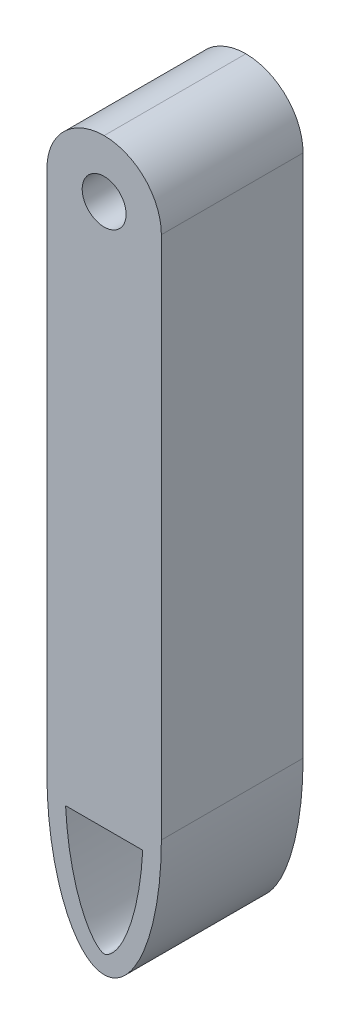
SolidWorks part; units mm, degrees
ref_plane "Front Plane" through (0, 0, 0) normal (0, 0, 1) x (1, 0, 0)
ref_plane "Top Plane" through (0, 0, 0) normal (0, 1, 0) x (1, 0, 0)
ref_plane "Right Plane" through (0, 0, 0) normal (1, 0, 0) x (0, 0, -1)
sketch "Sketch1" plane through (0, 0, 0) normal (0, 0, 1) x (1, 0, 0)
  line L1 (0, 0) -> (40, 0)
  line L2 (0, 0) -> (0, 203.2)
  line L3 (0, 203.2) -> (40, 203.2)
  line L4 (40, 0) -> (40, 203.2)
  dimension "D1" = 40
  dimension "D2" = 203.2
extrude "Boss-Extrude1" add sketch "Sketch1" along normal blind 49.53
fillet "Fillet1" radius 20 2 edges at (40, 203.2, 24.765) (0, 203.2, 24.765)
sketch "Sketch2" plane through (0, 0, 0) normal (0, 0, 1) x (1, 0, 0)
  circle A0 centre (20, 183.2) radius 7.67
  dimension "D1" = 15.34
extrude "Cut-Extrude2" cut sketch "Sketch2" against normal through all and the other way through all
sketch "Sketch3" plane through (0, 0, 0) normal (0, 0, 1) x (1, 0, 0)
  line L0 (0, 0) -> (40, 0) construction
  line L1 (0, 0) -> (40, 0)
  line L2 (6.5151, -6.35) -> (33.4849, -6.35)
  ellipse E0 centre (20, 0) end of major axis (20, -50.8) minor radius 20 (0, 0) -> (40, 0) ccw
  spline S0 degree 1 poles (6.5151, -6.35) (33.4849, -6.35) knots 0 0 1 1 construction
  spline S1 degree 3 poles (6.5151, -6.35) (6.5894, -7.7733) (6.7907, -10.6362) (7.3893, -16.1945) (8.4974, -22.8136) (10.3355, -29.8995) (12.575, -35.8439) (15.0406, -40.3695) (17.4453, -43.2431) (18.9523, -44.2064) (19.6506, -44.4267) (20, -44.4616) (20.3494, -44.4267) (21.0477, -44.2064) (22.5547, -43.2431) (24.9594, -40.3695) (27.425, -35.8439) (29.6645, -29.8995) (31.5026, -22.8136) (32.6107, -16.1945) (33.2093, -10.6362) (33.4106, -7.7733) (33.4849, -6.35) knots -1.438894 -1.438894 -1.438894 -1.438894 -1.348963 -1.259032 -1.07917 -0.899309 -0.719447 -0.539585 -0.359723 -0.179862 -0.089931 0 0.089931 0.179862 0.359723 0.539585 0.719447 0.899309 1.07917 1.259032 1.348963 1.438894 1.438894 1.438894 1.438894
  dimension "D1" = 50.8
  dimension "D2" = 6.35
extrude "Boss-Extrude2" add sketch "Sketch3" along normal through all
